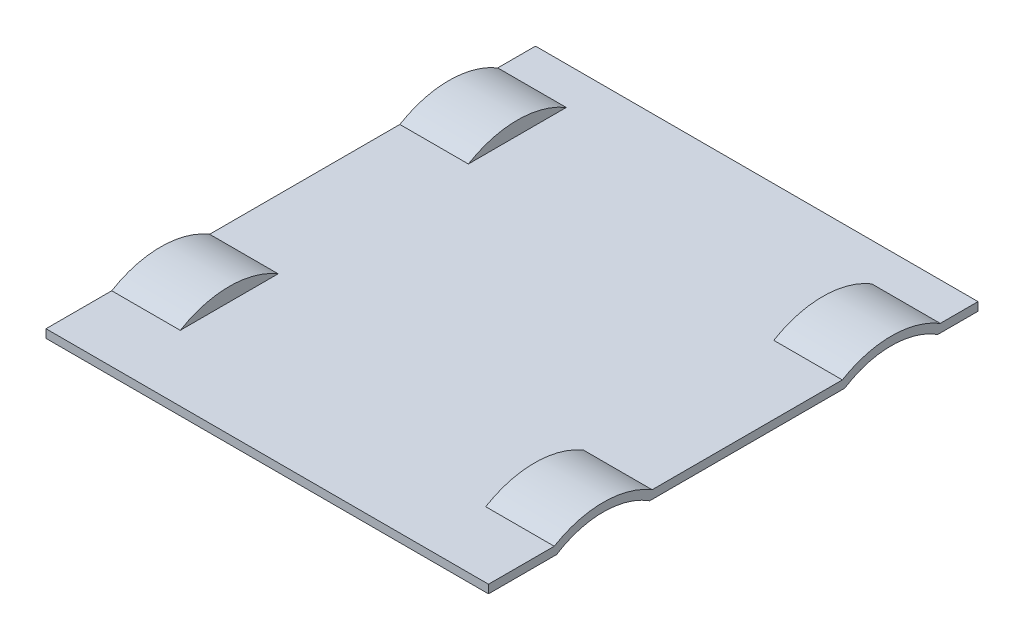
SolidWorks part; units mm, degrees
ref_plane "Front Plane" through (0, 0, 0) normal (0, 0, 1) x (1, 0, 0)
ref_plane "Top Plane" through (0, 0, 0) normal (0, 1, 0) x (1, 0, 0)
ref_plane "Right Plane" through (0, 0, 0) normal (1, 0, 0) x (0, 0, -1)
sketch "Sketch2" plane through (0, 0, 0) normal (1, 0, 0) x (0, 0, -1)
  line L0 (0, 0) -> (175, 0)
  line L1 (175, 0) -> (175, 3)
  line L2 (175, 3) -> (0, 3)
  line L3 (0, 3) -> (0, 0)
  line L4 (47.8374, -27.65) -> (29.7671, -23.6857) construction
  line L6 (17.3146, -46.15) -> (64.6854, -46.15) construction
  circle A0 centre (41, -26.15) radius 31
  circle A1 centre (144, -26.15) radius 31
  circle A2 centre (47.8374, -27.65) radius 18.5 construction
  circle A4 centre (41, -26.15) radius 3.5 construction
  arc A6 (62.7296, 0) -> (19.2704, 0) centre (41, -26.15) ccw
  arc A7 (165.7296, 0) -> (122.2704, 0) centre (144, -26.15) ccw
  dimension "D3" = 62
  dimension "D4" = 37
  dimension "D5" = 7
  dimension "D1" = 175
  dimension "D2" = 3
  dimension "D6" = 7
  dimension "D7" = 20
  dimension "D8" = 27.65
  dimension "D9" = 41
  dimension "D10" = 3
extrude "Boss-Extrude1" add sketch "Sketch2" against normal blind 158.2 contours A6 L2 L3 L0 | L2 A6 L0 A0 | L0 A0 L2 | L0 A6 L2 A0 | A7 L2 A6 L0 | L2 A7 L0 A1 | L0 A1 L2 | L0 A7 L2 A1 | A7 L0 L1 L2 region at (0, 1.5495, -10.6702) region at (0, 1.5774, -24.3279) region at (0, 1.3915, -41) region at (0, 1.5774, -57.6721) region at (0, 1.5332, -92.5) region at (0, 1.5774, -127.3279) region at (0, 1.3915, -144) region at (0, 1.5774, -160.6721) region at (0, 1.5935, -169.2989)
extrude "Boss-Extrude2" add sketch "Sketch2<5>" against normal blind 24.5 contours L2 A6 A0 | L2 A0 | L2 A7 A1 | L2 A1 region at (0, 5.3096, -41) region at (0, 3.7419, -41) region at (0, 5.3096, -144) region at (0, 3.7419, -144)
sketch "Sketch2<5>" plane through (0, 0, 0) normal (1, 0, 0) x (0, 0, -1) same geometry as "Sketch2"
extrude "Cut-Extrude1" cut sketch "Sketch2<7>" against normal blind 22 contours L0 A0 L2 | L2 A0 | L0 A1 L2 | L2 A1 region at (0, 1.3915, -41) region at (0, 3.7419, -41) region at (0, 3.7419, -144) region at (0, 1.3915, -144)
sketch "Sketch2<7>" plane through (0, 0, 0) normal (1, 0, 0) x (0, 0, -1) same geometry as "Sketch2"
ref_plane "Plane1" through (-79.1, 0, 0) normal (1, 0, 0) x (0, 0, -1)
mirror "Mirror1" about plane through (-79.1, 0, 0) normal (1, 0, 0) of "Cut-Extrude1", "Boss-Extrude2"
equation "\"D7@Sketch2\"=62/2-11"
equation "\"D9@Sketch2\"=62/2+10"
equation "\"D1@Boss-Extrude2\"=22.5+2"
